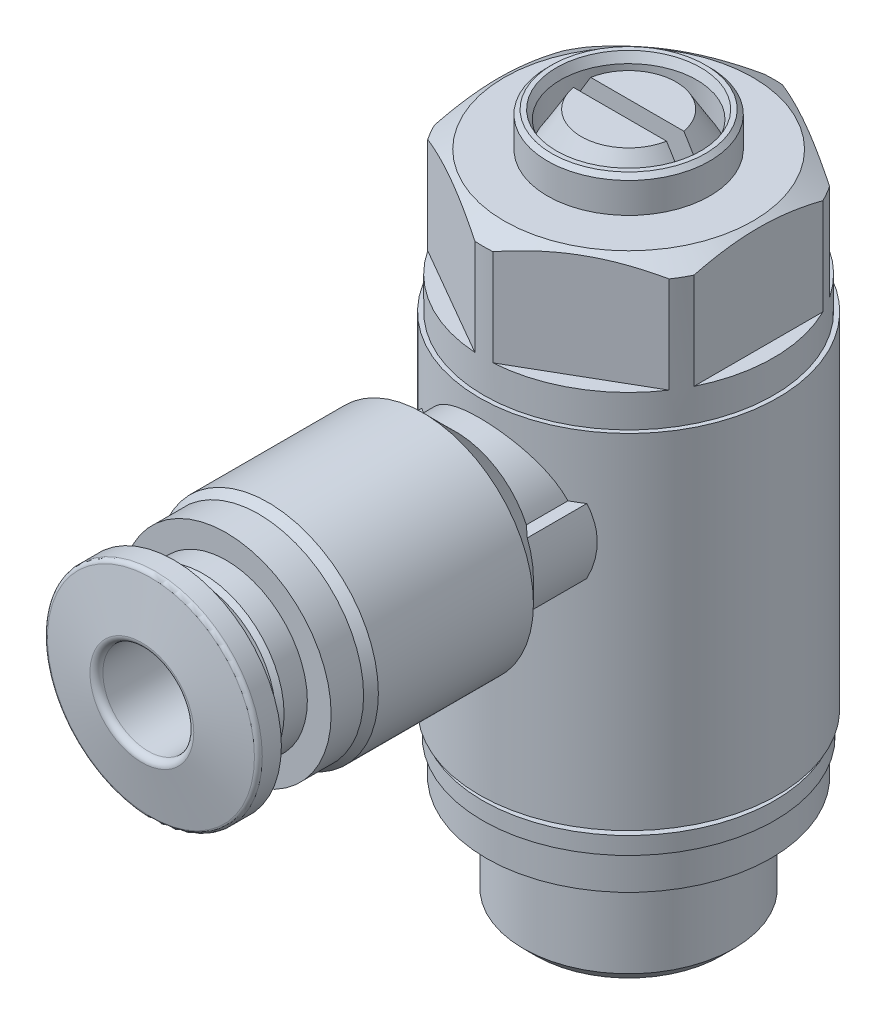
SolidWorks part; units mm, degrees
ref_plane "Ebene vorne" through (0, 0, 0) normal (0, 0, 1) x (1, 0, 0)
ref_plane "Ebene oben" through (0, 0, 0) normal (0, 1, 0) x (1, 0, 0)
ref_plane "Ebene rechts" through (0, 0, 0) normal (1, 0, 0) x (0, 0, -1)
sketch "Skizze1" plane through (0, 0, 0) normal (1, 0, 0) x (0, 0, -1)
  line L0 (0, 12.5) -> (2.1915, 12.5)
  line L1 (2.1915, 12.5) -> (3.15, 10.9)
  line L2 (3.15, 10.9) -> (3.15, 12.1)
  line L3 (3.15, 12.1) -> (3.3365, 12.5)
  line L4 (3.3365, 12.5) -> (3.55, 12.5)
  line L5 (3.55, 12.5) -> (3.75, 12.3)
  line L6 (3.75, 12.3) -> (3.75, 10.9)
  line L7 (3.75, 10.9) -> (5.75, 10.9)
  line L8 (5.75, 10.9) -> (6.7, 10.3515)
  line L9 (6.7, 10.3515) -> (6.7, 4.4)
  line L10 (6.7, 4.4) -> (6.9, 4.4)
  line L11 (6.9, 4.4) -> (6.9, -11.5)
  line L12 (6.9, -11.5) -> (6.075, -11.5)
  line L13 (6.375, -11.8) -> (6.75, -11.8)
  line L14 (6.75, -11.8) -> (6.75, -12.6)
  line L15 (6.75, -12.6) -> (6.575, -12.6)
  line L16 (6.575, -12.6) -> (6.575, -14.2)
  line L17 (6.575, -14.2) -> (4.864, -14.2)
  line L18 (4.864, -14.2) -> (4.864, -18.669)
  line L19 (4.864, -18.669) -> (4.283, -19.25)
  line L20 (4.283, -19.25) -> (0, -19.25)
  line L21 (0, -19.25) -> (0, 12.5)
  line L22 (0, -19.25) -> (0, 12.5) construction
  arc A0 (6.075, -11.5) -> (6.375, -11.8) centre (6.375, -11.5) ccw
revolve "Rotation1" add sketch "Skizze1" angle 360 about L22 reverse direction yes
cosmetic thread "Gewindedarstellung1" parameters "D1"=5.05, "D2"=8.566
ref_plane "Ebene1" through (0, 12.5, 0) normal (0, 1, 0) x (1, 0, 0)
sketch "Skizze2" plane through (0, 12.5, 0) normal (0, 1, 0) x (1, 0, 0)
  line L0 (-3.0741, -0.4) -> (3.0741, -0.4)
  line L1 (3.0741, 0.4) -> (-3.0741, 0.4)
  arc A0 (-3.0741, 0.4) -> (-3.0741, -0.4) centre (0, 0) ccw
  arc A1 (3.0741, -0.4) -> (3.0741, 0.4) centre (0, 0) ccw
extrude "Schnitt-Linear austragen1" cut sketch "Skizze2" against normal blind 1.2
sketch "Skizze3" plane through (0, 12.5, 0) normal (0, 1, 0) x (1, 0, 0)
  line L0 (-12, -12) -> (12, -12)
  line L1 (12, -12) -> (12, 12)
  line L2 (12, 12) -> (-12, 12)
  line L3 (-12, 12) -> (-12, -12)
  line L4 (-6, -3.4641) -> (0, -6.9282)
  line L5 (0, -6.9282) -> (6, -3.4641)
  line L6 (6, -3.4641) -> (6, 3.4641)
  line L7 (6, 3.4641) -> (0, 6.9282)
  line L8 (0, 6.9282) -> (-6, 3.4641)
  line L9 (-6, 3.4641) -> (-6, -3.4641)
extrude "Schnitt-Linear austragen2" cut sketch "Skizze3" against normal blind 6.6
sketch "Skizze4" plane through (0, 0, 0) normal (1, 0, 0) x (0, 0, -1)
  line L0 (-22.5, 0) -> (-22.5, 2.4)
  line L1 (-22.5, 2.4) -> (-22.0795, 4.7847)
  line L2 (-21.8825, 4.95) -> (-21, 4.95)
  line L3 (-21, 4.95) -> (-21, 3.1)
  line L4 (-20.6, 2.7) -> (-19.875, 2.7)
  line L5 (-19.875, 2.7) -> (-19.875, 3.55)
  line L6 (-19.875, 3.55) -> (-19.675, 3.75)
  line L7 (-19.675, 3.75) -> (-18.6, 3.75)
  line L8 (-18.6, 3.75) -> (-18.6, 4.85)
  line L9 (-18.6, 4.85) -> (-17.1, 4.85)
  line L10 (-17.1, 4.85) -> (-16.667, 5.1)
  line L11 (-16.667, 5.1) -> (-9.5, 5.1)
  line L12 (-9.5, 5.1) -> (-8, 3.6)
  line L13 (-8, 3.6) -> (0, 3.6)
  line L14 (0, 3.6) -> (0, 0)
  line L15 (0, 0) -> (-22.5, 0)
  line L16 (0, 0) -> (-22.5, 0) construction
  arc A0 (-22.0795, 4.7847) -> (-21.8825, 4.95) centre (-21.8825, 4.75) cw
  arc A1 (-21, 3.1) -> (-20.6, 2.7) centre (-20.6, 3.1) ccw
revolve "Rotation2" add sketch "Skizze4" angle 360 about L16 reverse direction yes
sketch "Skizze5" plane through (0, 0, 0) normal (0, 0, 1) x (1, 0, 0)
  line L0 (-3.8158, -1.5) -> (3.8158, -1.5)
  line L1 (3.8158, 1.5) -> (-3.8158, 1.5)
  arc A0 (-3.8158, 1.5) -> (-3.8158, -1.5) centre (0, 0) ccw
  arc A1 (3.8158, -1.5) -> (3.8158, 1.5) centre (0, 0) ccw
extrude "Aufsatz-Linear austragen1" add sketch "Skizze5" along normal blind 11.25
sketch "Skizze6" plane through (0, 0, 0) normal (1, 0, 0) x (0, 0, -1)
  line L0 (-22.5, 0) -> (-22.5, 2.4)
  line L1 (-22.2, 2.1) -> (-7.5, 2.1)
  line L2 (-7.5, 2.1) -> (-7.5, 1.5)
  line L3 (-7.5, 1.5) -> (0, 1.5)
  line L4 (0, 1.5) -> (0, 0)
  line L5 (0, 0) -> (-22.5, 0)
  line L6 (0, 0) -> (-22.5, 0) construction
  arc A0 (-22.5, 2.4) -> (-22.2, 2.1) centre (-22.2, 2.4) ccw
revolve "Schnitt-Rotation1" cut sketch "Skizze6" angle 360 about L6 reverse direction yes
sketch "Skizze7" plane through (0, 0, 0) normal (1, 0, 0) x (0, 0, -1)
  line L0 (1.5, 0.1) -> (1.5, -19.05)
  line L1 (1.5, -19.05) -> (1.6155, -19.25)
  line L2 (1.6155, -19.25) -> (0, -19.25)
  line L3 (0, -19.25) -> (0, 1.6)
  line L4 (0, -19.25) -> (0, 1.6) construction
  arc A0 (0, 1.6) -> (1.5, 0.1) centre (0, 0.1) cw
revolve "Schnitt-Rotation2" cut sketch "Skizze7" angle 360 about L4 reverse direction yes
ref_plane "Ebene2" through (0, 5.6, 0) normal (0, 1, 0) x (1, 0, 0)
ref_plane "Ebene3" through (0, 0, 22.5) normal (0, 0, 1) x (1, 0, 0)
sketch "Skizze8" plane through (0, 0, 0) normal (0, 0, 1) x (1, 0, 0)
  line L0 (-2.95, 11) -> (2.95, 11)
  line L1 (2.95, 11) -> (2.95, 11.5)
  line L2 (2.95, 11.5) -> (-2.95, 11.5)
  line L3 (-2.95, 11.5) -> (-2.95, 11)
extrude "Schnitt-Linear austragen3" cut sketch "Skizze8" along normal blind 0.4 and the other way blind 0.4
ref_plane "Ebene4" through (0, -14.2, 0) normal (0, 1, 0) x (1, 0, 0)
ref_plane "Ebene5" through (0, -19.25, 0) normal (0, 1, 0) x (1, 0, 0)
ref_plane "Ebene6" through (0, 0, 7.5) normal (0, 0, 1) x (1, 0, 0)
ref_plane "Anbau XY" through (0, -14.2, 0) normal (0, -1, 0) x (-1, 0, 0)
ref_plane "Anbau XZ" through (0, 0, 0) normal (0, 0, -1) x (-1, 0, 0)
ref_plane "Anbau YZ" through (0, 0, 0) normal (1, 0, 0) x (0, 0, -1)
ref_axis "Anbau X" through (-80.9, -14.2, 0) along (1, 0, 0)
ref_axis "Anbau Y" through (0, -14.2, -50) along (0, 0, 1)
ref_axis "Anbau Z" through (0, -50, 0) along (0, 1, 0)
sketch3d "Anbau"
  point P0 (0, -14.2, 0)
ref_plane "FDT_MOUNT XY" through (0, -14.2, 0) normal (0, 1, 0) x (1, 0, 0)
ref_plane "FDT_MOUNT XZ" through (0, 0, 0) normal (0, 0, -1) x (-1, 0, 0)
ref_plane "FDT_MOUNT YZ" through (0, 0, 0) normal (-1, 0, 0) x (0, 0, 1)
ref_axis "FDT_MOUNT X" through (80.9, -14.2, 0) along (-1, 0, 0)
ref_axis "FDT_MOUNT Y" through (0, -14.2, -50) along (0, 0, 1)
ref_axis "FDT_MOUNT Z" through (0, 50, 0) along (0, -1, 0)
sketch3d "FDT_MOUNT"
  point P0 (0, -14.2, 0)
ref_plane "FDT_SCHLAUCH XY" through (0, 0, 7.5) normal (0, 0, 1) x (1, 0, 0)
ref_plane "FDT_SCHLAUCH XZ" through (0, 0, 0) normal (0, -1, 0) x (-1, 0, 0)
ref_plane "FDT_SCHLAUCH YZ" through (0, 0, 0) normal (1, 0, 0) x (0, 0, -1)
ref_axis "FDT_SCHLAUCH X" through (-80.9, 0, 7.5) along (1, 0, 0)
ref_axis "FDT_SCHLAUCH Y" through (0, -50, 7.5) along (0, 1, 0)
ref_axis "FDT_SCHLAUCH Z" through (0, 0, 80.9) along (0, 0, -1)
sketch3d "FDT_SCHLAUCH"
  point P0 (0, 0, 7.5)
ref_plane "Schlauch XY" through (0, 0, 22.5) normal (0, 0, 1) x (1, 0, 0)
ref_plane "Schlauch XZ" through (0, 0, 0) normal (0, -1, 0) x (-1, 0, 0)
ref_plane "Schlauch YZ" through (0, 0, 0) normal (1, 0, 0) x (0, 0, -1)
ref_axis "Schlauch X" through (-80.9, 0, 22.5) along (1, 0, 0)
ref_axis "Schlauch Y" through (0, -50, 22.5) along (0, 1, 0)
ref_axis "Schlauch Z" through (0, 0, 80.9) along (0, 0, -1)
sketch3d "Schlauch"
  point P0 (0, 0, 22.5)
ref_plane "Zylinder XY" through (0, -19.25, 0) normal (0, -1, 0) x (-1, 0, 0)
ref_plane "Zylinder XZ" through (0, 0, 0) normal (0, 0, -1) x (-1, 0, 0)
ref_plane "Zylinder YZ" through (0, 0, 0) normal (1, 0, 0) x (0, 0, -1)
ref_axis "Zylinder X" through (-80.9, -19.25, 0) along (1, 0, 0)
ref_axis "Zylinder Y" through (0, -19.25, -50) along (0, 0, 1)
ref_axis "Zylinder Z" through (0, -50, 0) along (0, 1, 0)
sketch3d "Zylinder"
  point P0 (0, -19.25, 0)
